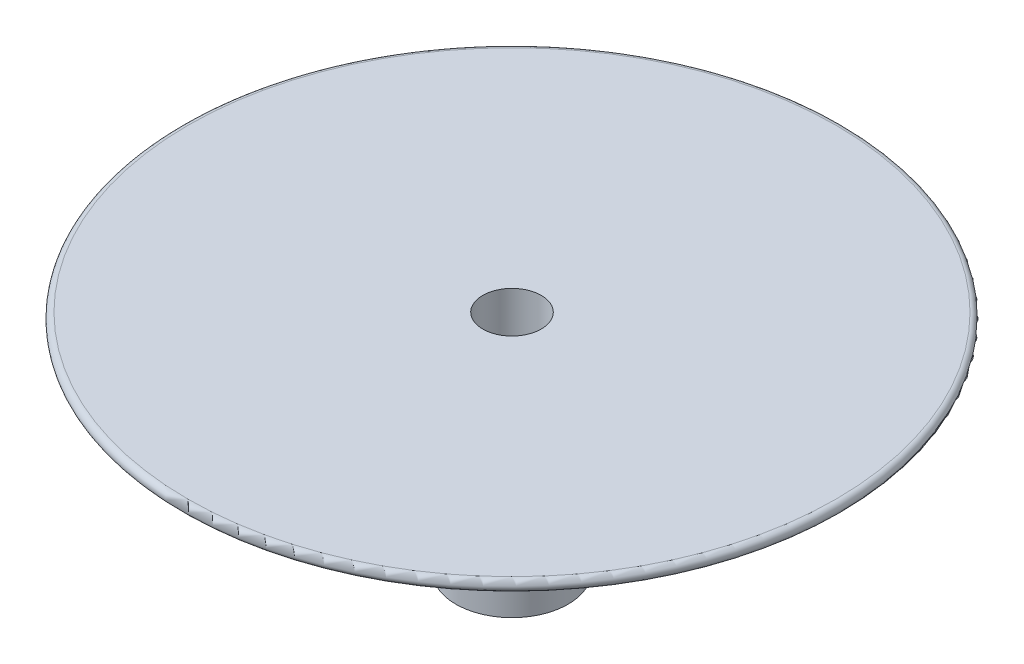
SolidWorks part; units mm, degrees
ref_plane "Front Plane" through (0, 0, 0) normal (0, 0, 1) x (1, 0, 0)
ref_plane "Top Plane" through (0, 0, 0) normal (0, 1, 0) x (1, 0, 0)
ref_plane "Right Plane" through (0, 0, 0) normal (1, 0, 0) x (0, 0, -1)
sketch "Sketch1" plane through (0, 0, 0) normal (0, 0, 1) x (1, 0, 0)
  line L0 (0, 10) -> (0, 0)
  line L1 (0, 10) -> (30.3313, 10)
  line L2 (0, 0) -> (0, -10)
  line L3 (0, -10) -> (5, -10)
  line L4 (5, -10) -> (5, 0)
  arc A1 (5, 0) -> (30.3313, 10) centre (0, 49.7494) ccw
  dimension "D1" = 50
  dimension "D2" = 10
  dimension "D3" = 5
  dimension "D4" = 10
revolve "Revolve1" add sketch "Sketch1" angle 360 about L0
sketch "Sketch2" plane through (0, 10, 0) normal (0, 1, 0) x (1, 0, 0)
  circle A0 centre (0, 0) radius 2.6
  dimension "D1" = 5.2
extrude "Cut-Extrude1" cut sketch "Sketch2" against normal through all
fillet "Fillet1" radius 0.5 1 edges at (-30.3313, 10, 0)
